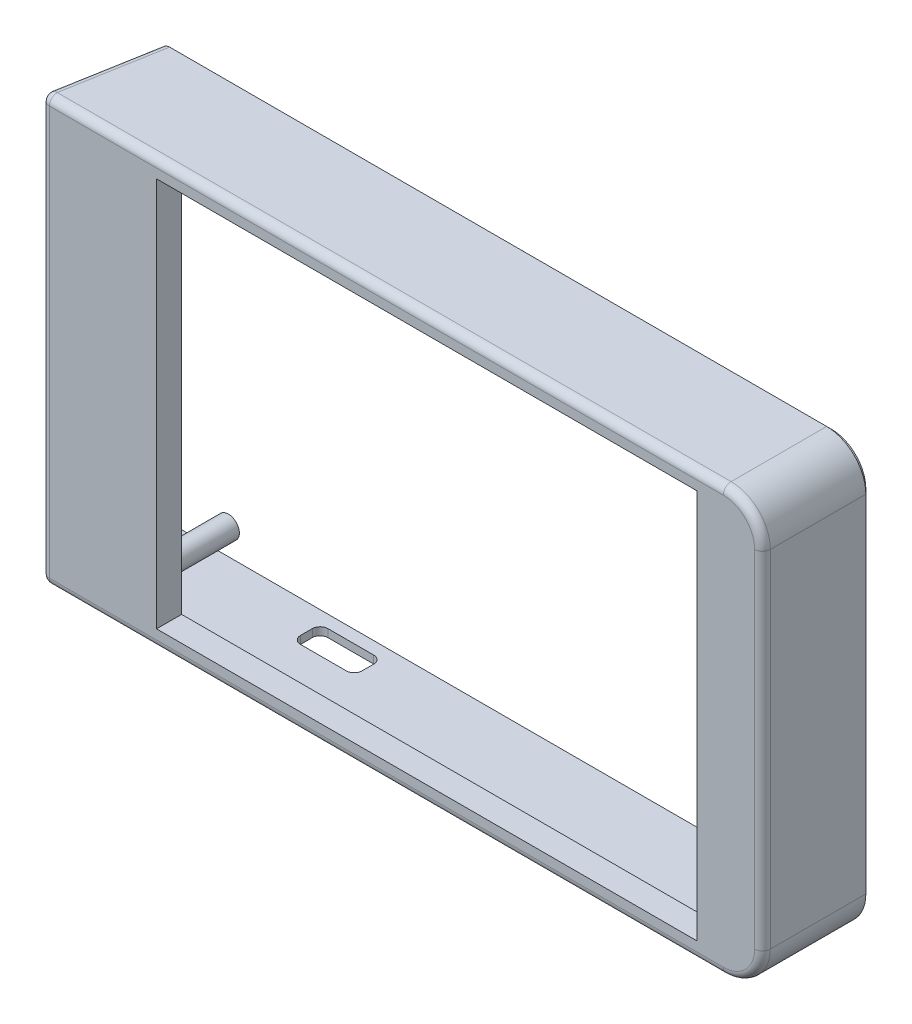
SolidWorks part; units mm, degrees
ref_plane "Front Plane" through (0, 0, 0) normal (0, 0, 1) x (1, 0, 0)
ref_plane "Top Plane" through (0, 0, 0) normal (0, 1, 0) x (1, 0, 0)
ref_plane "Right Plane" through (0, 0, 0) normal (1, 0, 0) x (0, 0, -1)
sketch "Sketch1" plane through (0, 0, 0) normal (0, 0, 1) x (1, 0, 0)
  line L0 (-26.1642, 66.7032) -> (-26.1642, 75.9234) construction
  line L1 (-38.9084, 23.9298) -> (50.9944, 23.9298)
  line L2 (-38.9084, 23.9298) -> (-38.9084, 78.1234)
  line L3 (-38.9084, 78.1234) -> (50.9944, 78.1234)
  line L4 (50.9944, 23.9298) -> (50.9944, 78.1234)
  line L5 (-26.3642, 76.1234) -> (42.8476, 76.1234)
  line L6 (-26.3642, 76.1234) -> (-26.3642, 25.9616)
  line L7 (-26.3642, 25.9616) -> (42.8476, 25.9616)
  line L8 (42.8476, 76.1234) -> (42.8476, 25.9616)
  line L9 (-26.1642, 75.9234) -> (42.8476, 75.9234) construction
  line L10 (42.8476, 75.9234) -> (42.8476, 25.9616) construction
  line L11 (42.8476, 25.9616) -> (-26.1642, 25.9616) construction
  line L13 (48.9944, 25.9298) -> (-36.9084, 25.9298) construction
  line L14 (-36.9084, 25.9298) -> (-36.9084, 76.0694) construction
  line L15 (48.9944, 76.0694) -> (48.9944, 25.9298) construction
  dimension "D1" = 2
  dimension "D2" = 2
  dimension "D3" = 0.2
  dimension "D4" = 0.2
  dimension "D5" = 0
  dimension "D6" = 0
  dimension "D7" = 2
  dimension "D8" = 2
extrude "Boss-Extrude1" add sketch "Sketch1" along normal blind 3.2
sketch "Sketch2" plane through (0, 0, 0) normal (0, 0, -1) x (-1, 0, 0)
  line L0 (35.994, 65.7633) -> (35.994, 64.1758) construction
  line L1 (36.994, 69.7796) -> (32.5145, 69.7796)
  line L2 (36.994, 69.7796) -> (36.994, 34.2196)
  line L3 (36.994, 34.2196) -> (32.5145, 34.2196)
  line L4 (32.5145, 69.7796) -> (32.5145, 34.2196)
  line L5 (33.5145, 68.4777) -> (33.5145, 33.5215) construction
  line L6 (33.9303, 68.7796) -> (35.5178, 68.7796) construction
  line L7 (35.5178, 33.2196) -> (33.9303, 33.2196) construction
  dimension "D1" = 1
  dimension "D2" = 1
  dimension "D3" = 1
  dimension "D4" = 1
extrude "Cut-Extrude1" cut sketch "Sketch2" against normal blind 2
sketch "Sketch3" plane through (0, 0, 0) normal (0, 0, -1) x (-1, 0, 0)
  line L1 (-50.9944, 78.1234) -> (38.9084, 78.1234)
  line L2 (-50.9944, 78.1234) -> (-50.9944, 23.9298)
  line L3 (-50.9944, 23.9298) -> (38.9084, 23.9298)
  line L4 (38.9084, 78.1234) -> (38.9084, 23.9298)
  line L5 (-49.9944, 77.1234) -> (37.9084, 77.1234)
  line L6 (-49.9944, 77.1234) -> (-49.9944, 24.9298)
  line L7 (-49.9944, 24.9298) -> (37.9084, 24.9298)
  line L8 (37.9084, 77.1234) -> (37.9084, 24.9298)
  dimension "D1" = 1
  dimension "D2" = 1
  dimension "D3" = 1
  dimension "D4" = 1
extrude "Boss-Extrude2" add sketch "Sketch3" along normal blind 10
sketch "Sketch4" plane through (0, 0, 0) normal (0, 0, -1) x (-1, 0, 0)
  line L0 (-48.9944, 50.9996) -> (35.9922, 50.9996) construction
  line L1 (-48.9944, 76.0694) -> (-48.9944, 25.9298) construction
  line L2 (35.9922, 33.5215) -> (35.9922, 68.4777) construction
  circle A0 centre (-45.9083, 29.0413) radius 1.4
  circle A2 centre (-45.9083, 72.9579) radius 1.4
  circle A3 centre (30.1901, 29.0413) radius 1.4
  circle A4 centre (30.1901, 72.9579) radius 1.4
  dimension "D1" = 2.8
extrude "Boss-Extrude3" add sketch "Sketch4" along normal offset from surface (9.8 mm away) 0.2
sketch "Sketch5" plane through (0, 23.9298, 0) normal (0, -1, 0) x (1, 0, 0)
  line L0 (-17.4834, -6) -> (-17.4834, -8.5) construction
  line L1 (-17.6834, -9) -> (-9.8334, -9)
  line L2 (-17.6834, -9) -> (-17.6834, -5.5)
  line L3 (-17.6834, -5.5) -> (-9.8334, -5.5)
  line L4 (-9.8334, -9) -> (-9.8334, -5.5)
  line L5 (-10.0334, -6) -> (-10.0334, -8.5) construction
  line L6 (-17.4834, -6) -> (-10.0334, -6) construction
  line L7 (-17.4834, -8.5) -> (-10.0334, -8.5) construction
  dimension "D1" = 0.2
  dimension "D2" = 0.2
  dimension "D3" = 0.5
  dimension "D4" = 0.5
extrude "Cut-Extrude2" cut sketch "Sketch5" against normal up to surface (1 mm away) up to face at (6.043, 24.9298, -5)
sketch "Sketch6" plane through (0, 23.9298, 0) normal (0, -1, 0) x (-1, 0, 0)
  line L0 (38.9084, 10) -> (41.236, -3.2)
  line L1 (41.236, -3.2) -> (38.9084, -3.2)
  line L2 (38.9084, -3.2) -> (38.9084, 10)
  line L3 (38.9084, -3.2) -> (-50.9944, -3.2) construction
  dimension "D1" = 80
extrude "Boss-Extrude4" add sketch "Sketch6" against normal up to surface (54.1936 mm away) up to face at (6.043, 78.1234, -3.4)
fillet "Fillet1" radius 4 2 edges at (49.9944, 77.1234, -5) (49.9944, 24.9298, -5)
fillet "Fillet2" radius 5 2 edges at (50.9944, 23.9298, -3.4) (50.9944, 78.1234, -3.4)
fillet "Fillet3" radius 1 5 edges at (2.3792, 23.9298, 3.2) (49.5299, 25.3943, 3.2) (50.9944, 51.0266, 3.2) (49.5299, 76.659, 3.2) (2.3792, 78.1234, 3.2)
sketch "Sketch7" plane through (0, 0, -9.8) normal (0, 0, -1) x (-1, 0, 0)
  circle A0 centre (-45.9083, 29.0413) radius 0.7
  circle A1 centre (-45.9083, 72.9579) radius 0.7
  circle A2 centre (30.1901, 72.9579) radius 0.7
  circle A3 centre (30.1901, 29.0413) radius 0.7
  dimension "D1" = 1.4
extrude "Cut-Extrude3" cut sketch "Sketch7" against normal blind 6
fillet "Fillet4" radius 1 5 edges at (-39.984, 23.9298, -3.9) (-41.1843, 24.2227, 2.9071) (-41.236, 51.0266, 3.2) (-41.1843, 77.8305, 2.9071) (-39.984, 78.1234, -3.9)
fillet "Fillet5" radius 1 4 edges at (-17.6834, 24.4298, -5.5) (-17.6834, 24.4298, -9) (-9.8334, 24.4298, -9) (-9.8334, 24.4298, -5.5)
sketch "Sketch9" plane through (0, 0, -10) normal (0, 0, -1) x (-1, 0, 0)
  line L0 (-45.9944, 77.1234) -> (37.9084, 77.1234)
  line L1 (37.9084, 77.1234) -> (37.9084, 24.9298)
  line L2 (37.9084, 24.9298) -> (-45.9944, 24.9298)
  line L3 (-49.9944, 73.1234) -> (-49.9944, 28.9298)
  line L4 (38.3084, 77.5234) -> (-45.9944, 77.5234)
  line L5 (-50.3944, 73.1234) -> (-50.3944, 28.9298)
  line L6 (-45.9944, 24.5298) -> (38.3084, 24.5298)
  line L7 (38.3084, 24.5298) -> (38.3084, 77.5234)
  arc A0 (-49.9944, 73.1234) -> (-45.9944, 77.1234) centre (-45.9944, 73.1234) cw
  arc A1 (-49.9944, 28.9298) -> (-45.9944, 24.9298) centre (-45.9944, 28.9298) ccw
  arc A2 (-49.9944, 28.9298) -> (-45.9944, 24.9298) centre (-45.9944, 28.9298) ccw construction
  arc A3 (-45.9944, 77.1234) -> (-49.9944, 73.1234) centre (-45.9944, 73.1234) ccw construction
  arc A4 (-50.3944, 73.1234) -> (-45.9944, 77.5234) centre (-45.9944, 73.1234) cw
  arc A5 (-50.3944, 28.9298) -> (-45.9944, 24.5298) centre (-45.9944, 28.9298) ccw
  dimension "D1" = 0.4
  dimension "D2" = 0.4
  dimension "D3" = 0.4
  dimension "D4" = 0.4
extrude "Boss-Extrude6" add sketch "Sketch9" along normal blind 0.6
fillet "Fillet6" radius 0.4 2 edges at (-38.3084, 77.5234, -10.3) (-38.3084, 24.5298, -10.3)
sketch "Sketch10" plane through (0, 0, 3.2) normal (0, 0, 1) x (1, 0, 0)
  line L0 (-26.3642, 26.1616) -> (-26.3642, 25.9616)
  line L1 (-26.3642, 76.1234) -> (42.8476, 76.1234)
  line L2 (-26.3642, 76.1234) -> (-26.3642, 75.9234)
  line L3 (-26.3642, 25.9616) -> (42.8476, 25.9616)
  line L4 (42.8476, 76.1234) -> (42.8476, 25.9616)
  line L5 (-26.3642, 75.9234) -> (42.6476, 75.9234)
  line L7 (-26.3642, 26.1616) -> (42.6476, 26.1616)
  line L8 (42.6476, 75.9234) -> (42.6476, 26.1616)
  dimension "D1" = 0.2
  dimension "D2" = 0.2
  dimension "D3" = 0.2
extrude "Boss-Extrude7" add sketch "Sketch10" against normal up to surface (3.2 mm away) up to face at (-28.7901, 72.9579, 0)
